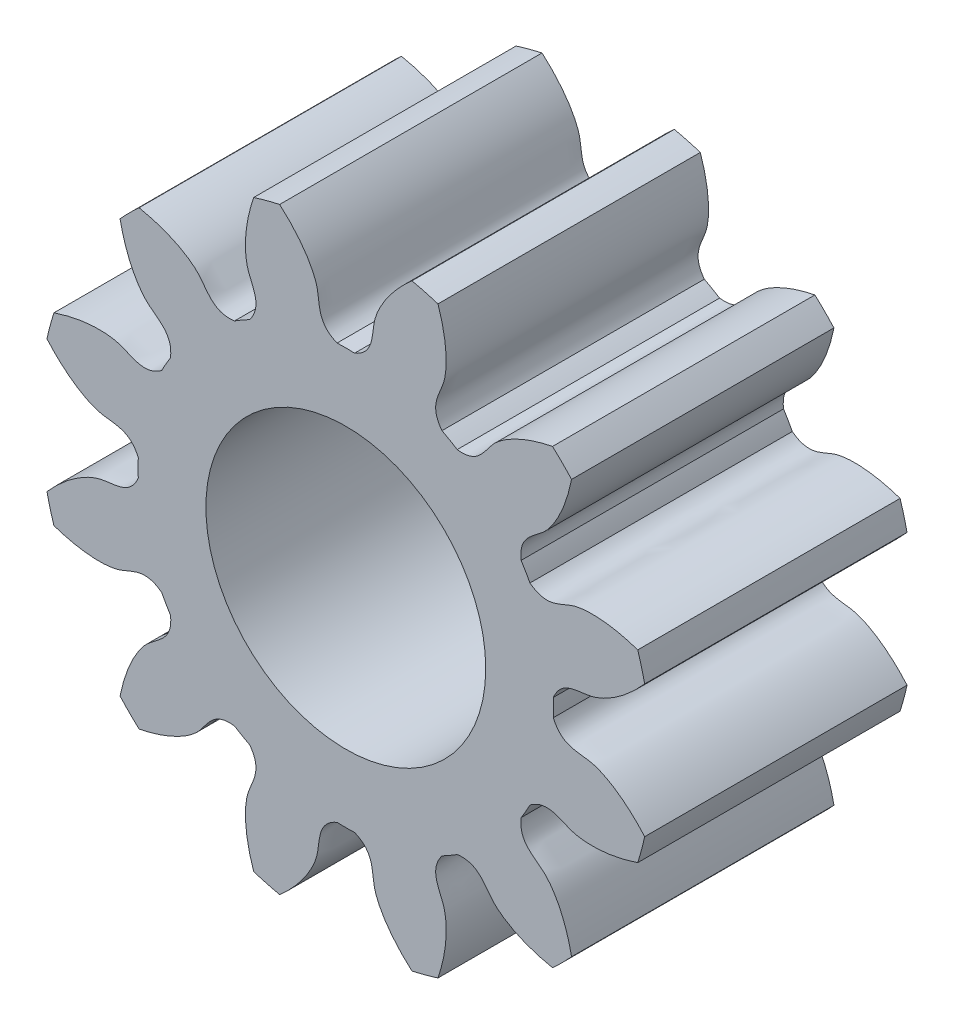
SolidWorks part; units mm, degrees
ref_plane "前视基准面" through (0, 0, 0) normal (0, 0, 1) x (1, 0, 0)
ref_plane "上视基准面" through (0, 0, 0) normal (0, 1, 0) x (1, 0, 0)
ref_plane "右视基准面" through (0, 0, 0) normal (1, 0, 0) x (0, 0, -1)
other "Configuration Table"
sketch "草图1" plane through (0, 0, 0) normal (0, 0, 1) x (1, 0, 0)
  circle A0 centre (0, 0) radius 3.5
extrude "凸台-拉伸1" add sketch "草图1" along normal blind 3
ref_axis "基准轴1" through (0, 0, 3) along (0, 0, -1)
sketch "草图2" plane through (0, 0, 0) normal (0, 0, 1) x (1, 0, 0)
  line L0 (0, 0) -> (0, 3.5) construction
  circle A0 centre (0, 0) radius 3.5 construction
  arc A1 (0.1004, 2.3729) -> (-0.1004, 2.3729) centre (0, 0) ccw
  arc A2 (1.7488, 3.9475) -> (-1.7488, 3.9475) centre (0, 0) ccw
  spline S0 degree 3 poles (0.1004, 2.3729) (0.3404, 2.4747) (0.2872, 2.6724) (0.3381, 2.8447) (0.3413, 2.855) (0.3451, 2.8662) (0.3495, 2.8784) (0.3546, 2.8915) (0.3603, 2.9056) (0.3668, 2.9206) (0.374, 2.9366) (0.3821, 2.9533) (0.3909, 2.971) (0.4007, 2.9894) (0.4114, 3.0086) (0.423, 3.0286) (0.4356, 3.0493) (0.4492, 3.0707) (0.4639, 3.0928) (0.4796, 3.1155) (0.4965, 3.1388) (0.5145, 3.1626) (0.5337, 3.187) (0.554, 3.2119) (0.5756, 3.2372) (0.5985, 3.2629) (0.6226, 3.289) (0.648, 3.3154) (0.6748, 3.342) (0.7028, 3.369) (0.7323, 3.3961) (0.7631, 3.4234) (0.7954, 3.4507) (0.829, 3.4782) (0.8641, 3.5057) (0.9006, 3.5331) (0.9385, 3.5604) (0.978, 3.5877) (1.0189, 3.6147) (1.0613, 3.6416) (1.1052, 3.6681) (1.1506, 3.6944) (1.1975, 3.7203) (1.2459, 3.7457) (1.2958, 3.7707) (1.3472, 3.7952) (1.4001, 3.8191) (1.4546, 3.8424) (1.5105, 3.865) (1.5679, 3.8869) (1.6472, 3.9154) (1.7078, 3.9351) (1.7488, 3.9475) knots 0 0 0 0 0.218015 0.222044 0.226546 0.231522 0.236972 0.242897 0.249295 0.256167 0.263513 0.271332 0.279626 0.288394 0.297636 0.307351 0.317541 0.328204 0.339341 0.350953 0.363038 0.375597 0.38863 0.402137 0.416118 0.430573 0.445502 0.460904 0.476781 0.493132 0.509956 0.527255 0.545027 0.563273 0.581994 0.601188 0.620856 0.640998 0.661614 0.682704 0.704268 0.726305 0.748817 0.771803 0.795262 0.819196 0.843603 0.868484 0.89384 0.919669 0.945972 1 1 1 1
  spline S1 degree 3 poles (-0.1004, 2.3729) (-0.3404, 2.4747) (-0.2872, 2.6724) (-0.3381, 2.8447) (-0.3413, 2.855) (-0.3451, 2.8662) (-0.3495, 2.8784) (-0.3546, 2.8915) (-0.3603, 2.9056) (-0.3668, 2.9206) (-0.374, 2.9366) (-0.3821, 2.9533) (-0.3909, 2.971) (-0.4007, 2.9894) (-0.4114, 3.0086) (-0.423, 3.0286) (-0.4356, 3.0493) (-0.4492, 3.0707) (-0.4639, 3.0928) (-0.4796, 3.1155) (-0.4965, 3.1388) (-0.5145, 3.1626) (-0.5337, 3.187) (-0.554, 3.2119) (-0.5756, 3.2372) (-0.5985, 3.2629) (-0.6226, 3.289) (-0.648, 3.3154) (-0.6748, 3.342) (-0.7028, 3.369) (-0.7323, 3.3961) (-0.7631, 3.4234) (-0.7954, 3.4507) (-0.829, 3.4782) (-0.8641, 3.5057) (-0.9006, 3.5331) (-0.9385, 3.5604) (-0.978, 3.5877) (-1.0189, 3.6147) (-1.0613, 3.6416) (-1.1052, 3.6681) (-1.1506, 3.6944) (-1.1975, 3.7203) (-1.2459, 3.7457) (-1.2958, 3.7707) (-1.3472, 3.7952) (-1.4001, 3.8191) (-1.4546, 3.8424) (-1.5105, 3.865) (-1.5679, 3.8869) (-1.6472, 3.9154) (-1.7078, 3.9351) (-1.7488, 3.9475) knots 0 0 0 0 0.218015 0.222044 0.226546 0.231522 0.236972 0.242897 0.249295 0.256167 0.263513 0.271332 0.279626 0.288394 0.297636 0.307351 0.317541 0.328204 0.339341 0.350953 0.363038 0.375597 0.38863 0.402137 0.416118 0.430573 0.445502 0.460904 0.476781 0.493132 0.509956 0.527255 0.545027 0.563273 0.581994 0.601188 0.620856 0.640998 0.661614 0.682704 0.704268 0.726305 0.748817 0.771803 0.795262 0.819196 0.843603 0.868484 0.89384 0.919669 0.945972 1 1 1 1
extrude "切除-拉伸1" cut sketch "草图2" along normal through all
pattern_circular "阵列(圆周)1" count 12 over 360 about axis through (0, 0, 3) along (0, 0, -1) of "切除-拉伸1"
sketch "草图3" plane through (0, 0, 0) normal (0, 0, 1) x (1, 0, 0)
  circle A0 centre (0, 0) radius 3 construction
  dimension "Dn" = 6
sketch "草图5" plane through (0, 0, 3) normal (0, 0, 1) x (1, 0, 0)
  circle A0 centre (0, 0) radius 1.6
  dimension "D1" = 3.2
extrude "切除-拉伸2" cut sketch "草图5" against normal up to next
